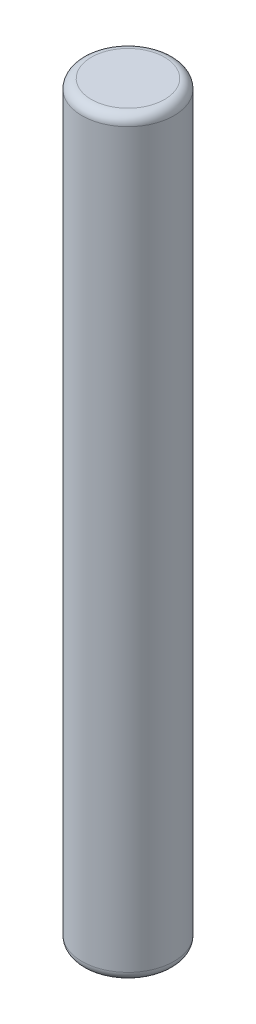
SolidWorks part; units mm, degrees
material "ABS"
ref_plane "Front Plane" through (0, 0, 0) normal (0, 0, 1) x (1, 0, 0)
ref_plane "Top Plane" through (0, 0, 0) normal (0, 1, 0) x (1, 0, 0)
ref_plane "Right Plane" through (0, 0, 0) normal (1, 0, 0) x (0, 0, -1)
sketch "Sketch1" plane through (0, 0, 0) normal (0, 1, 0) x (1, 0, 0)
  circle A0 centre (0, 0) radius 2.45
  dimension "D1" = 4.9
extrude "Boss-Extrude1" add sketch "Sketch1" along normal blind 40
fillet "Fillet1" radius 0.5 2 edges at (0, 0, 2.45) (0, 40, 2.45)
